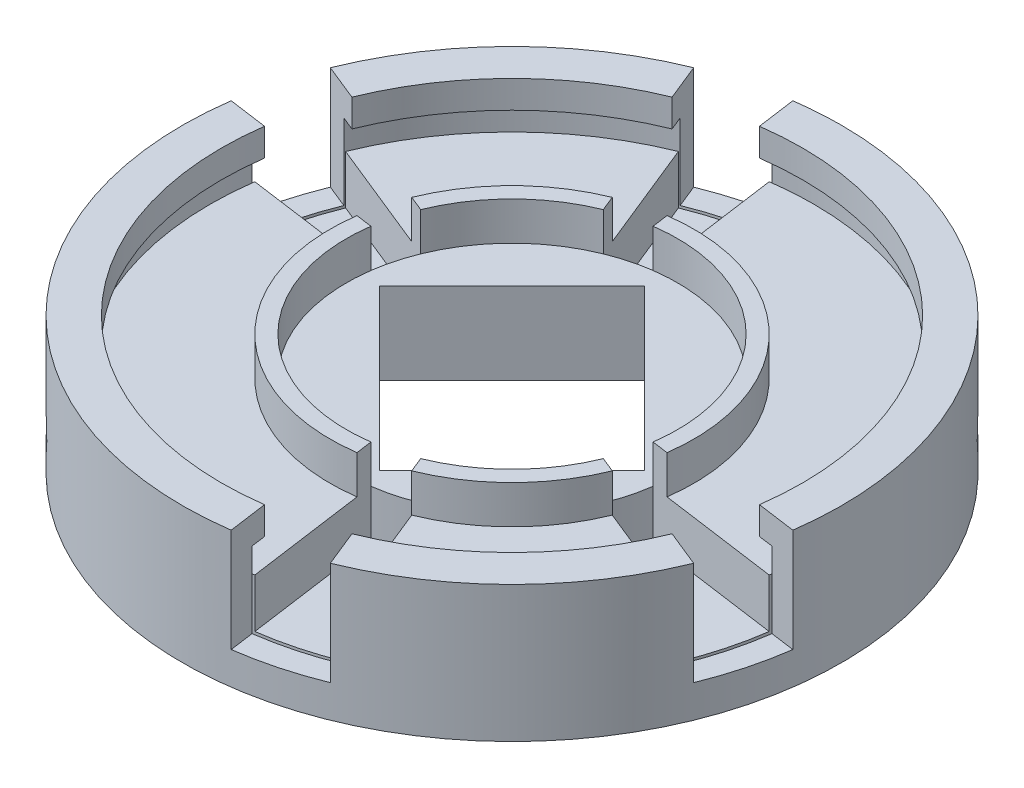
SolidWorks part; units mm, degrees
other "outer_ring"
other "inner_ring"
ref_plane "Front Plane" through (0, 0, 0) normal (0, 0, 1) x (1, 0, 0)
ref_plane "Top Plane" through (0, 0, 0) normal (0, 1, 0) x (1, 0, 0)
ref_plane "Right Plane" through (0, 0, 0) normal (1, 0, 0) x (0, 0, -1)
sketch "Sketch1" plane through (0, 0, 0) normal (0, 0, 1) x (1, 0, 0)
  line L4 (17.5401, 1.65) -> (17.5401, 3.34)
  line L5 (17.5401, 3.34) -> (19.9401, 3.34)
  line L6 (19.9401, 3.34) -> (19.9401, -5)
  line L7 (19.9401, -5) -> (-0.2599, -5)
  line L9 (10.8901, 0) -> (18.4401, 0)
  line L10 (16.9401, 3.15) -> (16.9401, 1.55) construction
  line L11 (10.8901, 0) -> (10.8901, 2.35)
  line L15 (-0.2599, 0) -> (-0.2599, -5)
  line L16 (18.2401, 0) -> (18.2401, 1.55) construction
  line L18 (9.8901, 2.35) -> (9.8901, 0)
  line L19 (18.4401, 0) -> (18.4401, 1.65)
  line L20 (9.8901, 0) -> (-0.2599, 0)
  line L21 (-18.7599, 1.55) -> (18.2401, 1.55) construction
  line L22 (-0.2599, -998.45) -> (-0.2599, 49001.55) construction
  line L23 (10.8901, -4) -> (10.8901, 0)
  line L24 (10.8901, -4) -> (-0.2599, -4)
  line L25 (18.4401, 0) -> (18.4401, -5)
  line L27 (10.8901, 2.35) -> (9.8901, 2.35)
  line L28 (9.2788, 3.15) -> (9.2788, 1.55) construction
  line L30 (18.4401, 1.65) -> (17.5401, 1.65)
  line L31 (18.2401, -5) -> (18.2401, 0)
  line L32 (-18.7599, 0) -> (18.2401, 0) construction
  line L33 (11.0901, 0) -> (11.0901, 1.55) construction
  point P8 (0, 0)
  point P24 (9.2788, 2.35)
  point P28 (-0.2599, 1.55)
  dimension "D1" = 5
  dimension "D2" = 0.6
  dimension "D3" = 1.69
  dimension "D4" = 0.2
  dimension "D5" = 1
  dimension "D6" = 0.1
  dimension "D7" = 0.7
  dimension "D8" = 4
  dimension "D9" = 1.5
  dimension "D10" = 0.2
revolve "Revolve1" add sketch "Sketch1" angle 360 about L22 region at (19.06, -0.4696, 0)
revolve "Revolve3" add sketch "Sketch1<4>" angle 360 about L22 region at (12.4119, -2.9656, 0) region at (5.5691, -1.8411, 0)
sketch "Sketch1<4>" plane through (0, 0, 0) normal (0, 0, 1) x (1, 0, 0) same geometry as "Sketch1"
sketch "Sketch4" plane through (0, -5, 0) normal (0, -1, 0) x (1, 0, 0)
  circle A0 centre (-7.3664, -7.7428) radius 1.6
  circle A1 centre (7.4829, 7.1064) radius 1.6
  dimension "D1" = 3.2
extrude "Cut-Extrude1" cut sketch "Sketch4" against normal blind 4
sketch "Sketch5" plane through (0, -5, 0) normal (0, -1, 0) x (1, 0, 0)
  line L0 (3.8236, -13.877) -> (-9.2225, -0.8309)
  line L1 (3.8236, -13.877) -> (13.617, -4.0835)
  line L2 (-9.2225, -0.8309) -> (0.5709, 8.9626)
  line L3 (13.617, -4.0835) -> (0.5709, 8.9626)
  line L6 (-6.2704, 0) -> (-0.2599, 6.0104) construction
  line L7 (3.1165, -11.0485) -> (1.773, -9.705) construction
  line L8 (9.3744, -6.2049) -> (4.5307, -11.0485) construction
  line L10 (-3.2652, 3.0052) -> (-4.3258, 4.0659) construction
  dimension "D1" = 1.5
  dimension "D2" = 1.5
  dimension "D4" = 1.5
extrude "Cut-Extrude2" cut sketch "Sketch5" against normal blind 2.5
sketch "Sketch6" plane through (0, -2.5, 0) normal (0, -1, 0) x (1, 0, 0)
  line L0 (-9.2225, -0.8309) -> (0.5709, 8.9626)
  line L1 (-9.2225, -0.8309) -> (-1.0908, -8.9626)
  line L2 (0.5709, 8.9626) -> (8.7026, 0.8309)
  line L3 (-1.0908, -8.9626) -> (8.7026, 0.8309)
  line L4 (0.3234, -5.427) -> (5.1671, -0.5834) construction
  line L6 (-9.2225, -0.8309) -> (3.8236, -13.877) construction
  point P8 (-8.6725, -0.5572)
  point P9 (-9.2225, -0.8309)
  point P11 (0.5709, 8.9626)
  point P12 (0.5709, 8.9626)
  point P13 (-9.2225, -0.8309)
  point P17 (0.5709, 8.9626)
  point P19 (0.5709, 8.9626)
  dimension "D1" = 1.5
extrude "Cut-Extrude3" cut sketch "Sketch6" against normal through all
sketch "Sketch10" plane through (0, 3.34, 0) normal (0, 1, 0) x (1, 0, 0)
  line L0 (-3.0515, 20.0062) -> (-1.6626, 10.0526)
  line L1 (-4.0715, 9.4072) -> (-7.8455, 18.7216)
  line L2 (-1.5659, 20.2135) -> (-4.5371, 19.7989) construction
  line L3 (-9.2357, 18.1584) -> (-6.4553, 19.2849) construction
  circle A0 centre (-0.2599, 0) radius 20.2 construction
  circle A1 centre (-0.2599, 0) radius 10.15
  arc A2 (-1.6626, 10.0526) -> (-4.0715, 9.4072) centre (-0.2599, 0) ccw
  arc A3 (-3.0515, 20.0062) -> (-7.8455, 18.7216) centre (-0.2599, 0) ccw
  circle A4 centre (-0.2599, 0) radius 10.15 construction
  point P12 (-3.0515, 20.0062)
  point P13 (2.6066, 19.7614)
  point P16 (-7.8455, 18.7216)
  point P17 (-0.1906, 10.3498)
  point P20 (6.7503, 18.1963)
  point P21 (3.2523, 19.1811)
  point P22 (6.2269, 18.3894)
  point P23 (-7.6569, 18.0426)
  point P24 (-2.7564, 19.3395)
  dimension "D2" = 3
  dimension "D1" = 0
extrude "Cut-Extrude6" cut sketch "Sketch10" against normal offset from surface (6.34 mm away) 2 up to face at (-0.2599, -5, -18.7)
pattern_circular "CirPattern2" count 12 over 360 about axis through (-0.2599, -998.45, 0) along (0, -1, 0) skipping 1, 2, 3, 5, 7, 8, 9, 11 of "Cut-Extrude6"
ref_plane "Plane6" through (-0.13, 0, 0.13) normal (-0.7071, 0, 0.7071) x (0.7071, 0, 0.7071)
ref_plane "Plane7" through (-0.13, 0, -0.13) normal (0.7071, 0, 0.7071) x (0.7071, 0, -0.7071)
ref_plane "Plane8" through (14.1536, 0, -14.1536) normal (0.7071, 0, -0.7071) x (-0.7071, 0, -0.7071)
sketch "Sketch13" plane through (14.1536, 0, -14.1536) normal (0.7071, 0, -0.7071) x (-0.7071, 0, -0.7071)
  line L0 (-18.3162, -5) -> (18.6838, -5) construction
  line L1 (0.1838, -5) -> (0.1838, 0) construction
  line L3 (14.9476, 0) -> (-14.58, 0) construction
  circle A0 centre (0.1838, -2.5) radius 1.6
  point P4 (0, 0)
  point P5 (0, 0)
  point P8 (-19.5315, -6.303)
  point P9 (0, 0)
  point P10 (0, 0)
  point P12 (0.1838, -2.5)
  point P14 (0, 0)
  point P15 (0, 0)
  dimension "D1" = 3.2
extrude "Cut-Extrude7" cut sketch "Sketch13" against normal blind 4.5
sketch "Sketch14" plane through (14.1536, 0, -14.1536) normal (0.7071, 0, -0.7071) x (-0.7071, 0, -0.7071)
  circle A0 centre (0.1838, -2.5) radius 1.15
  circle A2 centre (0.1838, -2.5) radius 1.6 construction
  point P2 (0, 0)
  point P3 (0, 0)
  point P4 (0, 0)
  point P5 (0, 0)
  dimension "D1" = 2.3
extrude "Cut-Extrude10" cut sketch "Sketch14" along normal through all both and the other way through all
mirror "Mirror1" about plane through (-0.13, 0, 0.13) normal (-0.7071, 0, 0.7071) of "Cut-Extrude7"
